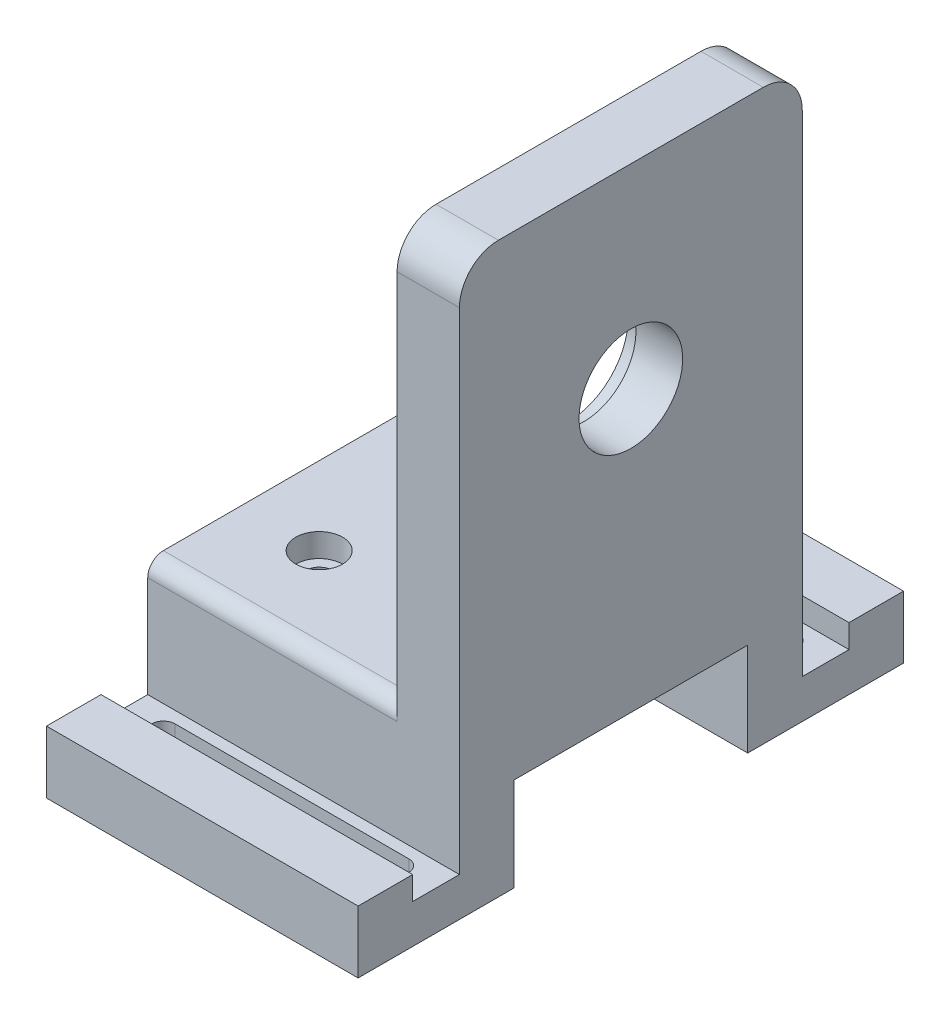
SolidWorks part; units mm, degrees
ref_plane "Front Plane" through (0, 0, 0) normal (0, 0, 1) x (1, 0, 0)
ref_plane "Top Plane" through (0, 0, 0) normal (0, 1, 0) x (1, 0, 0)
ref_plane "Right Plane" through (0, 0, 0) normal (1, 0, 0) x (0, 0, -1)
sketch "Sketch1" plane through (0, 0, 0) normal (0, 1, 0) x (1, 0, 0)
  line L1 (-10, 10) -> (10, 10) construction
  line L2 (-10, 10) -> (-10, -10) construction
  line L3 (-10, -10) -> (10, -10) construction
  line L4 (10, 10) -> (10, -10) construction
  line L5 (-10, 10) -> (10, -10) construction
  line L6 (-10, -10) -> (10, 10) construction
  line L7 (20, 35) -> (-20, 35)
  line L8 (20, 35) -> (20, -35)
  line L9 (20, -35) -> (-20, -35)
  line L10 (-20, 35) -> (-20, -35)
  line L11 (20, 35) -> (-20, -35) construction
  line L12 (20, -35) -> (-20, 35) construction
  point P0 (0, 0)
  point P6 (0, 0)
  dimension "D1" = 20
  dimension "D2" = 20
  dimension "D3" = 70
  dimension "D4" = 40
extrude "Boss-Extrude1" add sketch "Sketch1" along normal blind 20
sketch "Sketch2" plane through (-20, 0, 0) normal (-1, 0, 0) x (0, 0, 1)
  line L1 (15, 12) -> (-15, 12)
  line L2 (15, 12) -> (15, -12)
  line L3 (15, -12) -> (-15, -12)
  line L4 (-15, 12) -> (-15, -12)
  line L5 (15, 12) -> (-15, -12) construction
  line L6 (15, -12) -> (-15, 12) construction
  point P0 (0, 0)
  dimension "D1" = 24
  dimension "D2" = 30
extrude "Cut-Extrude1" cut sketch "Sketch2" against normal through all
sketch "Sketch3" plane through (0, 20, 0) normal (0, 1, 0) x (1, 0, 0)
  line L1 (10, 10) -> (-10, 10) construction
  line L2 (10, 10) -> (10, -10) construction
  line L3 (10, -10) -> (-10, -10) construction
  line L4 (-10, 10) -> (-10, -10) construction
  line L5 (10, 10) -> (-10, -10) construction
  line L6 (10, -10) -> (-10, 10) construction
  circle A0 centre (-10, 10) radius 1.65
  circle A1 centre (10, 10) radius 1.65
  circle A2 centre (10, -10) radius 1.65
  circle A3 centre (-10, -10) radius 1.65
  point P0 (0, 0)
  dimension "D3" = 3.3
  dimension "D4" = 3.3
  dimension "D5" = 3.3
  dimension "D6" = 3.3
  dimension "D1" = 20
  dimension "D2" = 20
extrude "Cut-Extrude2" cut sketch "Sketch3" against normal through all
sketch "Sketch5" plane through (0, 20, 0) normal (0, 1, 0) x (1, 0, 0)
  circle A0 centre (-10, 10) radius 3
  circle A1 centre (10, 10) radius 3
  circle A2 centre (10, -10) radius 3
  circle A3 centre (-10, -10) radius 3
  dimension "D1" = 6
  dimension "D2" = 6
  dimension "D3" = 6
  dimension "D4" = 6
extrude "Cut-Extrude3" cut sketch "Sketch5" against normal blind 3
sketch "Sketch9" plane through (20, 0, 0) normal (1, 0, 0) x (0, 0, -1)
  line L0 (-35, 20) -> (35, 20) construction
  line L1 (22, 35) -> (28, 35)
  line L2 (22, 35) -> (22, 5)
  line L3 (22, 5) -> (28, 5)
  line L4 (28, 35) -> (28, 5)
  line L5 (22, 35) -> (28, 5) construction
  line L6 (22, 5) -> (28, 35) construction
  line L7 (15, 0) -> (35, 0) construction
  point P0 (25, 20)
  dimension "D1" = 6
  dimension "D2" = 5
extrude "Cut-Extrude6" cut sketch "Sketch9" against normal through all
sketch "Sketch10" plane through (0, 5, 0) normal (0, 1, 0) x (1, 0, 0)
  line L0 (15, 25) -> (-15, 25) construction
  line L1 (15, 23.5) -> (-15, 23.5)
  line L2 (15, 26.5) -> (-15, 26.5)
  line L3 (-20, 22) -> (20, 22) construction
  arc A0 (15, 23.5) -> (15, 26.5) centre (15, 25) ccw
  arc A1 (-15, 26.5) -> (-15, 23.5) centre (-15, 25) ccw
  point P2 (0, 25)
  dimension "D1" = 3
  dimension "D2" = 3
  dimension "D3" = 30
  dimension "D4" = 0
extrude "Cut-Extrude7" cut sketch "Sketch10" against normal blind 10
mirror "Mirror2" about plane through (0, 0, 0) normal (0, 0, 1) of "Cut-Extrude7", "Cut-Extrude6"
sketch "Sketch14" plane through (0, 20, 0) normal (0, 1, 0) x (1, 0, 0)
  line L0 (20, -22) -> (-20, -22) construction
  line L1 (12, 22) -> (20, 22)
  line L2 (12, 22) -> (12, -22)
  line L3 (12, -22) -> (20, -22)
  line L4 (20, 22) -> (20, -22)
  line L5 (12, 22) -> (20, -22) construction
  line L6 (12, -22) -> (20, 22) construction
  point P0 (16, 0)
  dimension "D1" = 8
  dimension "D2" = 16
extrude "Boss-Extrude3" add sketch "Sketch14" along normal blind 53
sketch "Sketch16" plane through (12, 0, 0) normal (-1, 0, 0) x (0, 0, 1)
  circle A0 centre (0, 48) radius 6.65
  dimension "D1" = 13.3
  dimension "D2" = 48
extrude "Cut-Extrude11" cut sketch "Sketch16" against normal through all
sketch "Sketch17" plane through (12, 0, 0) normal (-1, 0, 0) x (0, 0, 1)
  circle A0 centre (0, 48) radius 7.65
  dimension "D1" = 15.3
extrude "Cut-Extrude12" cut sketch "Sketch17" against normal blind 2
fillet "Fillet2" radius 5 2 edges at (16, 73, 22) (16, 73, -22)
ref_plane "Plane1" through (0, 38, 0) normal (0, 1, 0) x (1, 0, 0)
sketch "Sketch18" plane through (0, 38, 0) normal (0, 1, 0) x (1, 0, 0)
  circle A0 centre (10, 10) radius 3
  circle A1 centre (10, -10) radius 3
extrude "Cut-Extrude13" cut sketch "Sketch18" against normal up to surface (18 mm away) up to face at (-10, 20, 13)
chamfer "Chamfer1" distance 2 angle 45 2 edges at (12, 38, 10) (12, 38, -10)
sketch "Sketch19" plane through (20, 0, 0) normal (1, 0, 0) x (0, 0, -1)
  line L0 (-28, 5) -> (-28, 8) construction
  line L1 (-28, 5) -> (-28, 20) construction
  line L2 (-28, 8) -> (-35, 8)
  line L3 (-35, 20) -> (-35, 0) construction
  line L4 (-35, 8) -> (-35, 20)
  line L5 (-35, 20) -> (-28, 20)
  line L6 (-28, 20) -> (-28, 8)
  dimension "D1" = 3
extrude "Cut-Extrude14" cut sketch "Sketch19" against normal through all
mirror "Mirror3" about plane through (0, 0, 0) normal (0, 0, 1) of "Cut-Extrude14"
fillet "Fillet4" radius 2 2 edges at (-4, 20, 22) (-4, 20, -22)
